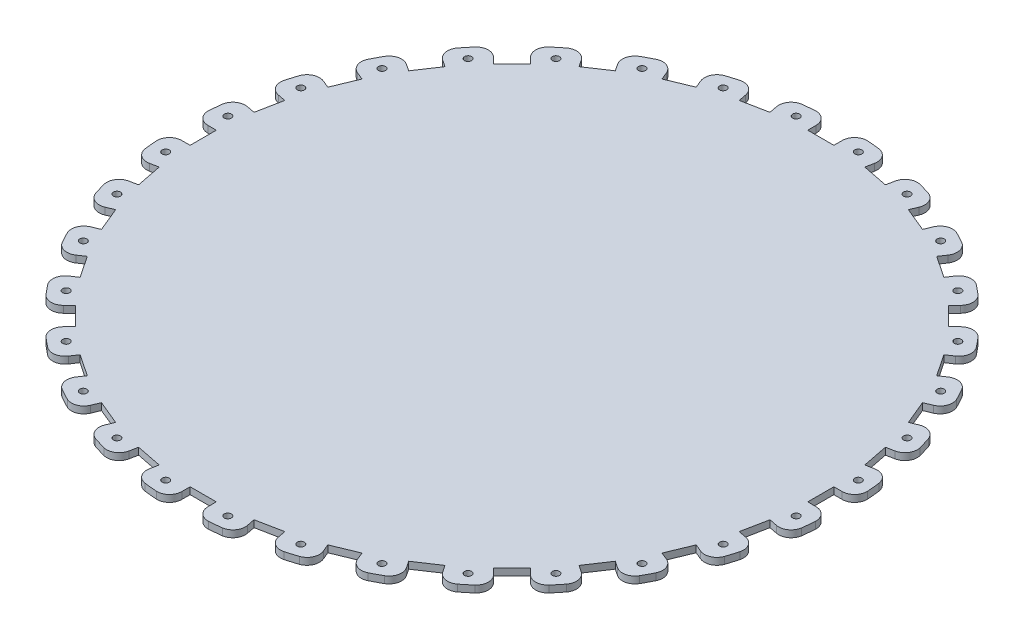
SolidWorks part; units mm, degrees
material "Maple"
ref_plane "Front" through (0, 0, 0) normal (0, 0, 1) x (1, 0, 0)
ref_plane "Top" through (0, 0, 0) normal (0, 1, 0) x (1, 0, 0)
ref_plane "Right" through (0, 0, 0) normal (1, 0, 0) x (0, 0, -1)
sketch "Sketch1" plane through (0, 0, 0) normal (0, 1, 0) x (1, 0, 0)
  line L0 (133.35, 0) -> (142.367, 0) construction
  line L1 (152.0161, 6.0325) -> (142.367, 6.0325)
  line L2 (150.272, -23.7403) -> (140.8083, -21.8578)
  line L3 (152.0161, -6.0325) -> (142.367, -6.0325)
  line L4 (142.367, 6.0325) -> (142.367, -6.0325)
  line L5 (133.35, 0) -> (142.367, -6.0325) construction
  line L6 (133.35, 0) -> (142.367, 6.0325) construction
  line L7 (147.9182, -35.5735) -> (138.4546, -33.691)
  line L8 (140.8083, -21.8578) -> (138.4546, -33.691)
  line L9 (130.7877, -26.0153) -> (139.6315, -27.7744) construction
  line L10 (130.7877, -26.0153) -> (138.4546, -33.691) construction
  line L11 (130.7877, -26.0153) -> (140.8083, -21.8578) construction
  line L12 (142.7531, -52.6007) -> (133.8385, -48.9082)
  line L13 (138.136, -63.7473) -> (129.2214, -60.0548)
  line L14 (133.8385, -48.9082) -> (129.2214, -60.0548)
  line L15 (123.1993, -51.0308) -> (131.53, -54.4815) construction
  line L16 (123.1993, -51.0308) -> (129.2214, -60.0548) construction
  line L17 (123.1993, -51.0308) -> (133.8385, -48.9082) construction
  line L18 (129.7482, -79.4398) -> (121.7253, -74.079)
  line L19 (123.0453, -89.4714) -> (115.0224, -84.1107)
  line L20 (121.7253, -74.079) -> (115.0224, -84.1107)
  line L21 (110.8765, -74.0853) -> (118.3738, -79.0949) construction
  line L22 (110.8765, -74.0853) -> (115.0224, -84.1107) construction
  line L23 (110.8765, -74.0853) -> (121.7253, -74.079) construction
  line L24 (111.7572, -103.226) -> (104.9343, -96.403)
  line L25 (103.226, -111.7572) -> (96.403, -104.9343)
  line L26 (104.9343, -96.403) -> (96.403, -104.9343)
  line L27 (94.2927, -94.2927) -> (100.6687, -100.6687) construction
  line L28 (94.2927, -94.2927) -> (96.403, -104.9343) construction
  line L29 (94.2927, -94.2927) -> (104.9343, -96.403) construction
  line L30 (89.4714, -123.0453) -> (84.1107, -115.0224)
  line L31 (79.4398, -129.7482) -> (74.079, -121.7253)
  line L32 (84.1107, -115.0224) -> (74.079, -121.7253)
  line L33 (74.0853, -110.8765) -> (79.0949, -118.3738) construction
  line L34 (74.0853, -110.8765) -> (74.079, -121.7253) construction
  line L35 (74.0853, -110.8765) -> (84.1107, -115.0224) construction
  line L36 (63.7473, -138.136) -> (60.0548, -129.2214)
  line L37 (52.6007, -142.7531) -> (48.9082, -133.8385)
  line L38 (60.0548, -129.2214) -> (48.9082, -133.8385)
  line L39 (51.0308, -123.1993) -> (54.4815, -131.53) construction
  line L40 (51.0308, -123.1993) -> (48.9082, -133.8385) construction
  line L41 (51.0308, -123.1993) -> (60.0548, -129.2214) construction
  line L42 (35.5735, -147.9182) -> (33.691, -138.4546)
  line L43 (23.7403, -150.272) -> (21.8578, -140.8083)
  line L44 (33.691, -138.4546) -> (21.8578, -140.8083)
  line L45 (26.0153, -130.7877) -> (27.7744, -139.6315) construction
  line L46 (26.0153, -130.7877) -> (21.8578, -140.8083) construction
  line L47 (26.0153, -130.7877) -> (33.691, -138.4546) construction
  line L48 (6.0325, -152.0161) -> (6.0325, -142.367)
  line L49 (-6.0325, -152.0161) -> (-6.0325, -142.367)
  line L50 (6.0325, -142.367) -> (-6.0325, -142.367)
  line L51 (0, -133.35) -> (0, -142.367) construction
  line L52 (0, -133.35) -> (-6.0325, -142.367) construction
  line L53 (0, -133.35) -> (6.0325, -142.367) construction
  line L54 (-23.7403, -150.272) -> (-21.8578, -140.8083)
  line L55 (-35.5735, -147.9182) -> (-33.691, -138.4546)
  line L56 (-21.8578, -140.8083) -> (-33.691, -138.4546)
  line L57 (-26.0153, -130.7877) -> (-27.7744, -139.6315) construction
  line L58 (-26.0153, -130.7877) -> (-33.691, -138.4546) construction
  line L59 (-26.0153, -130.7877) -> (-21.8578, -140.8083) construction
  line L60 (-52.6007, -142.7531) -> (-48.9082, -133.8385)
  line L61 (-63.7473, -138.136) -> (-60.0548, -129.2214)
  line L62 (-48.9082, -133.8385) -> (-60.0548, -129.2214)
  line L63 (-51.0308, -123.1993) -> (-54.4815, -131.53) construction
  line L64 (-51.0308, -123.1993) -> (-60.0548, -129.2214) construction
  line L65 (-51.0308, -123.1993) -> (-48.9082, -133.8385) construction
  line L66 (-79.4398, -129.7482) -> (-74.079, -121.7253)
  line L67 (-89.4714, -123.0453) -> (-84.1107, -115.0224)
  line L68 (-74.079, -121.7253) -> (-84.1107, -115.0224)
  line L69 (-74.0853, -110.8765) -> (-79.0949, -118.3738) construction
  line L70 (-74.0853, -110.8765) -> (-84.1107, -115.0224) construction
  line L71 (-74.0853, -110.8765) -> (-74.079, -121.7253) construction
  line L72 (-103.226, -111.7572) -> (-96.403, -104.9343)
  line L73 (-111.7572, -103.226) -> (-104.9343, -96.403)
  line L74 (-96.403, -104.9343) -> (-104.9343, -96.403)
  line L75 (-94.2927, -94.2927) -> (-100.6687, -100.6687) construction
  line L76 (-94.2927, -94.2927) -> (-104.9343, -96.403) construction
  line L77 (-94.2927, -94.2927) -> (-96.403, -104.9343) construction
  line L78 (-123.0453, -89.4714) -> (-115.0224, -84.1107)
  line L79 (-129.7482, -79.4398) -> (-121.7253, -74.079)
  line L80 (-115.0224, -84.1107) -> (-121.7253, -74.079)
  line L81 (-110.8765, -74.0853) -> (-118.3738, -79.0949) construction
  line L82 (-110.8765, -74.0853) -> (-121.7253, -74.079) construction
  line L83 (-110.8765, -74.0853) -> (-115.0224, -84.1107) construction
  line L84 (-138.136, -63.7473) -> (-129.2214, -60.0548)
  line L85 (-142.7531, -52.6007) -> (-133.8385, -48.9082)
  line L86 (-129.2214, -60.0548) -> (-133.8385, -48.9082)
  line L87 (-123.1993, -51.0308) -> (-131.53, -54.4815) construction
  line L88 (-123.1993, -51.0308) -> (-133.8385, -48.9082) construction
  line L89 (-123.1993, -51.0308) -> (-129.2214, -60.0548) construction
  line L90 (-147.9182, -35.5735) -> (-138.4546, -33.691)
  line L91 (-150.272, -23.7403) -> (-140.8083, -21.8578)
  line L92 (-138.4546, -33.691) -> (-140.8083, -21.8578)
  line L93 (-130.7877, -26.0153) -> (-139.6315, -27.7744) construction
  line L94 (-130.7877, -26.0153) -> (-140.8083, -21.8578) construction
  line L95 (-130.7877, -26.0153) -> (-138.4546, -33.691) construction
  line L96 (-152.0161, -6.0325) -> (-142.367, -6.0325)
  line L97 (-152.0161, 6.0325) -> (-142.367, 6.0325)
  line L98 (-142.367, -6.0325) -> (-142.367, 6.0325)
  line L99 (-133.35, 0) -> (-142.367, 0) construction
  line L100 (-133.35, 0) -> (-142.367, 6.0325) construction
  line L101 (-133.35, 0) -> (-142.367, -6.0325) construction
  line L102 (-150.272, 23.7403) -> (-140.8083, 21.8578)
  line L103 (-147.9182, 35.5735) -> (-138.4546, 33.691)
  line L104 (-140.8083, 21.8578) -> (-138.4546, 33.691)
  line L105 (-130.7877, 26.0153) -> (-139.6315, 27.7744) construction
  line L106 (-130.7877, 26.0153) -> (-138.4546, 33.691) construction
  line L107 (-130.7877, 26.0153) -> (-140.8083, 21.8578) construction
  line L108 (-142.7531, 52.6007) -> (-133.8385, 48.9082)
  line L109 (-138.136, 63.7473) -> (-129.2214, 60.0548)
  line L110 (-133.8385, 48.9082) -> (-129.2214, 60.0548)
  line L111 (-123.1993, 51.0308) -> (-131.53, 54.4815) construction
  line L112 (-123.1993, 51.0308) -> (-129.2214, 60.0548) construction
  line L113 (-123.1993, 51.0308) -> (-133.8385, 48.9082) construction
  line L114 (-129.7482, 79.4398) -> (-121.7253, 74.079)
  line L115 (-123.0453, 89.4714) -> (-115.0224, 84.1107)
  line L116 (-121.7253, 74.079) -> (-115.0224, 84.1107)
  line L117 (-110.8765, 74.0853) -> (-118.3738, 79.0949) construction
  line L118 (-110.8765, 74.0853) -> (-115.0224, 84.1107) construction
  line L119 (-110.8765, 74.0853) -> (-121.7253, 74.079) construction
  line L120 (-111.7572, 103.226) -> (-104.9343, 96.403)
  line L121 (-103.226, 111.7572) -> (-96.403, 104.9343)
  line L122 (-104.9343, 96.403) -> (-96.403, 104.9343)
  line L123 (-94.2927, 94.2927) -> (-100.6687, 100.6687) construction
  line L124 (-94.2927, 94.2927) -> (-96.403, 104.9343) construction
  line L125 (-94.2927, 94.2927) -> (-104.9343, 96.403) construction
  line L126 (-89.4714, 123.0453) -> (-84.1107, 115.0224)
  line L127 (-79.4398, 129.7482) -> (-74.079, 121.7253)
  line L128 (-84.1107, 115.0224) -> (-74.079, 121.7253)
  line L129 (-74.0853, 110.8765) -> (-79.0949, 118.3738) construction
  line L130 (-74.0853, 110.8765) -> (-74.079, 121.7253) construction
  line L131 (-74.0853, 110.8765) -> (-84.1107, 115.0224) construction
  line L132 (-63.7473, 138.136) -> (-60.0548, 129.2214)
  line L133 (-52.6007, 142.7531) -> (-48.9082, 133.8385)
  line L134 (-60.0548, 129.2214) -> (-48.9082, 133.8385)
  line L135 (-51.0308, 123.1993) -> (-54.4815, 131.53) construction
  line L136 (-51.0308, 123.1993) -> (-48.9082, 133.8385) construction
  line L137 (-51.0308, 123.1993) -> (-60.0548, 129.2214) construction
  line L138 (-35.5735, 147.9182) -> (-33.691, 138.4546)
  line L139 (-23.7403, 150.272) -> (-21.8578, 140.8083)
  line L140 (-33.691, 138.4546) -> (-21.8578, 140.8083)
  line L141 (-26.0153, 130.7877) -> (-27.7744, 139.6315) construction
  line L142 (-26.0153, 130.7877) -> (-21.8578, 140.8083) construction
  line L143 (-26.0153, 130.7877) -> (-33.691, 138.4546) construction
  line L144 (-6.0325, 152.0161) -> (-6.0325, 142.367)
  line L145 (6.0325, 152.0161) -> (6.0325, 142.367)
  line L146 (-6.0325, 142.367) -> (6.0325, 142.367)
  line L147 (0, 133.35) -> (0, 142.367) construction
  line L148 (0, 133.35) -> (6.0325, 142.367) construction
  line L149 (0, 133.35) -> (-6.0325, 142.367) construction
  line L150 (23.7403, 150.272) -> (21.8578, 140.8083)
  line L151 (35.5735, 147.9182) -> (33.691, 138.4546)
  line L152 (21.8578, 140.8083) -> (33.691, 138.4546)
  line L153 (26.0153, 130.7877) -> (27.7744, 139.6315) construction
  line L154 (26.0153, 130.7877) -> (33.691, 138.4546) construction
  line L155 (26.0153, 130.7877) -> (21.8578, 140.8083) construction
  line L156 (52.6007, 142.7531) -> (48.9082, 133.8385)
  line L157 (63.7473, 138.136) -> (60.0548, 129.2214)
  line L158 (48.9082, 133.8385) -> (60.0548, 129.2214)
  line L159 (51.0308, 123.1993) -> (54.4815, 131.53) construction
  line L160 (51.0308, 123.1993) -> (60.0548, 129.2214) construction
  line L161 (51.0308, 123.1993) -> (48.9082, 133.8385) construction
  line L162 (79.4398, 129.7482) -> (74.079, 121.7253)
  line L163 (89.4714, 123.0453) -> (84.1107, 115.0224)
  line L164 (74.079, 121.7253) -> (84.1107, 115.0224)
  line L165 (74.0853, 110.8765) -> (79.0949, 118.3738) construction
  line L166 (74.0853, 110.8765) -> (84.1107, 115.0224) construction
  line L167 (74.0853, 110.8765) -> (74.079, 121.7253) construction
  line L168 (103.226, 111.7572) -> (96.403, 104.9343)
  line L169 (111.7572, 103.226) -> (104.9343, 96.403)
  line L170 (96.403, 104.9343) -> (104.9343, 96.403)
  line L171 (94.2927, 94.2927) -> (100.6687, 100.6687) construction
  line L172 (94.2927, 94.2927) -> (104.9343, 96.403) construction
  line L173 (94.2927, 94.2927) -> (96.403, 104.9343) construction
  line L174 (123.0453, 89.4714) -> (115.0224, 84.1107)
  line L175 (129.7482, 79.4398) -> (121.7253, 74.079)
  line L176 (115.0224, 84.1107) -> (121.7253, 74.079)
  line L177 (110.8765, 74.0853) -> (118.3738, 79.0949) construction
  line L178 (110.8765, 74.0853) -> (121.7253, 74.079) construction
  line L179 (110.8765, 74.0853) -> (115.0224, 84.1107) construction
  line L180 (138.136, 63.7473) -> (129.2214, 60.0548)
  line L181 (142.7531, 52.6007) -> (133.8385, 48.9082)
  line L182 (129.2214, 60.0548) -> (133.8385, 48.9082)
  line L183 (123.1993, 51.0308) -> (131.53, 54.4815) construction
  line L184 (123.1993, 51.0308) -> (133.8385, 48.9082) construction
  line L185 (123.1993, 51.0308) -> (129.2214, 60.0548) construction
  line L186 (147.9182, 35.5735) -> (138.4546, 33.691)
  line L187 (150.272, 23.7403) -> (140.8083, 21.8578)
  line L188 (138.4546, 33.691) -> (140.8083, 21.8578)
  line L189 (130.7877, 26.0153) -> (139.6315, 27.7744) construction
  line L190 (130.7877, 26.0153) -> (140.8083, 21.8578) construction
  line L191 (130.7877, 26.0153) -> (138.4546, 33.691) construction
  arc A0 (152.2699, 6.297) -> (152.2699, -6.297) centre (0, 0) ccw
  circle A1 centre (0, 0) radius 133.35
  arc A2 (152.0161, 6.0325) -> (152.2699, 6.297) centre (152.0161, 6.2865) ccw
  arc A3 (152.0161, -6.0325) -> (152.2699, -6.297) centre (152.0161, -6.2865) cw
  arc A4 (150.272, -23.7403) -> (150.5725, -23.5304) centre (150.3216, -23.4912) ccw
  arc A5 (147.9182, -35.5735) -> (148.1155, -35.8824) centre (147.8687, -35.8226) cw
  arc A6 (142.7531, -52.6007) -> (143.0888, -52.4535) centre (142.8503, -52.3661) ccw
  arc A7 (138.136, -63.7473) -> (138.2692, -64.0888) centre (138.0388, -63.982) cw
  arc A8 (129.7482, -79.4398) -> (130.1062, -79.3608) centre (129.8893, -79.2286) ccw
  arc A9 (123.0453, -89.4714) -> (123.1093, -89.8324) centre (122.9041, -89.6826) cw
  arc A10 (111.7572, -103.226) -> (112.1237, -103.2184) centre (111.9368, -103.0464) ccw
  arc A11 (103.226, -111.7572) -> (103.2184, -112.1237) centre (103.0464, -111.9368) cw
  arc A12 (89.4714, -123.0453) -> (89.8324, -123.1093) centre (89.6826, -122.9041) ccw
  arc A13 (79.4398, -129.7482) -> (79.3608, -130.1062) centre (79.2286, -129.8893) cw
  arc A14 (63.7473, -138.136) -> (64.0888, -138.2692) centre (63.982, -138.0388) ccw
  arc A15 (52.6007, -142.7531) -> (52.4535, -143.0888) centre (52.3661, -142.8503) cw
  arc A16 (35.5735, -147.9182) -> (35.8824, -148.1155) centre (35.8226, -147.8687) ccw
  arc A17 (23.7403, -150.272) -> (23.5304, -150.5725) centre (23.4912, -150.3216) cw
  arc A18 (6.0325, -152.0161) -> (6.297, -152.2699) centre (6.2865, -152.0161) ccw
  arc A19 (-6.0325, -152.0161) -> (-6.297, -152.2699) centre (-6.2865, -152.0161) cw
  arc A20 (-23.7403, -150.272) -> (-23.5304, -150.5725) centre (-23.4912, -150.3216) ccw
  arc A21 (-35.5735, -147.9182) -> (-35.8824, -148.1155) centre (-35.8226, -147.8687) cw
  arc A22 (-52.6007, -142.7531) -> (-52.4535, -143.0888) centre (-52.3661, -142.8503) ccw
  arc A23 (-63.7473, -138.136) -> (-64.0888, -138.2692) centre (-63.982, -138.0388) cw
  arc A24 (-79.4398, -129.7482) -> (-79.3608, -130.1062) centre (-79.2286, -129.8893) ccw
  arc A25 (-89.4714, -123.0453) -> (-89.8324, -123.1093) centre (-89.6826, -122.9041) cw
  arc A26 (-103.226, -111.7572) -> (-103.2184, -112.1237) centre (-103.0464, -111.9368) ccw
  arc A27 (-111.7572, -103.226) -> (-112.1237, -103.2184) centre (-111.9368, -103.0464) cw
  arc A28 (-123.0453, -89.4714) -> (-123.1093, -89.8324) centre (-122.9041, -89.6826) ccw
  arc A29 (-129.7482, -79.4398) -> (-130.1062, -79.3608) centre (-129.8893, -79.2286) cw
  arc A30 (-138.136, -63.7473) -> (-138.2692, -64.0888) centre (-138.0388, -63.982) ccw
  arc A31 (-142.7531, -52.6007) -> (-143.0888, -52.4535) centre (-142.8503, -52.3661) cw
  arc A32 (-147.9182, -35.5735) -> (-148.1155, -35.8824) centre (-147.8687, -35.8226) ccw
  arc A33 (-150.272, -23.7403) -> (-150.5725, -23.5304) centre (-150.3216, -23.4912) cw
  arc A34 (-152.0161, -6.0325) -> (-152.2699, -6.297) centre (-152.0161, -6.2865) ccw
  arc A35 (-152.0161, 6.0325) -> (-152.2699, 6.297) centre (-152.0161, 6.2865) cw
  arc A36 (-150.272, 23.7403) -> (-150.5725, 23.5304) centre (-150.3216, 23.4912) ccw
  arc A37 (-147.9182, 35.5735) -> (-148.1155, 35.8824) centre (-147.8687, 35.8226) cw
  arc A38 (-142.7531, 52.6007) -> (-143.0888, 52.4535) centre (-142.8503, 52.3661) ccw
  arc A39 (-138.136, 63.7473) -> (-138.2692, 64.0888) centre (-138.0388, 63.982) cw
  arc A40 (-129.7482, 79.4398) -> (-130.1062, 79.3608) centre (-129.8893, 79.2286) ccw
  arc A41 (-123.0453, 89.4714) -> (-123.1093, 89.8324) centre (-122.9041, 89.6826) cw
  arc A42 (-111.7572, 103.226) -> (-112.1237, 103.2184) centre (-111.9368, 103.0464) ccw
  arc A43 (-103.226, 111.7572) -> (-103.2184, 112.1237) centre (-103.0464, 111.9368) cw
  arc A44 (-89.4714, 123.0453) -> (-89.8324, 123.1093) centre (-89.6826, 122.9041) ccw
  arc A45 (-79.4398, 129.7482) -> (-79.3608, 130.1062) centre (-79.2286, 129.8893) cw
  arc A46 (-63.7473, 138.136) -> (-64.0888, 138.2692) centre (-63.982, 138.0388) ccw
  arc A47 (-52.6007, 142.7531) -> (-52.4535, 143.0888) centre (-52.3661, 142.8503) cw
  arc A48 (-35.5735, 147.9182) -> (-35.8824, 148.1155) centre (-35.8226, 147.8687) ccw
  arc A49 (-23.7403, 150.272) -> (-23.5304, 150.5725) centre (-23.4912, 150.3216) cw
  arc A50 (-6.0325, 152.0161) -> (-6.297, 152.2699) centre (-6.2865, 152.0161) ccw
  arc A51 (6.0325, 152.0161) -> (6.297, 152.2699) centre (6.2865, 152.0161) cw
  arc A52 (23.7403, 150.272) -> (23.5304, 150.5725) centre (23.4912, 150.3216) ccw
  arc A53 (35.5735, 147.9182) -> (35.8824, 148.1155) centre (35.8226, 147.8687) cw
  arc A54 (52.6007, 142.7531) -> (52.4535, 143.0888) centre (52.3661, 142.8503) ccw
  arc A55 (63.7473, 138.136) -> (64.0888, 138.2692) centre (63.982, 138.0388) cw
  arc A56 (79.4398, 129.7482) -> (79.3608, 130.1062) centre (79.2286, 129.8893) ccw
  arc A57 (89.4714, 123.0453) -> (89.8324, 123.1093) centre (89.6826, 122.9041) cw
  arc A58 (103.226, 111.7572) -> (103.2184, 112.1237) centre (103.0464, 111.9368) ccw
  arc A59 (111.7572, 103.226) -> (112.1237, 103.2184) centre (111.9368, 103.0464) cw
  arc A60 (123.0453, 89.4714) -> (123.1093, 89.8324) centre (122.9041, 89.6826) ccw
  arc A61 (129.7482, 79.4398) -> (130.1062, 79.3608) centre (129.8893, 79.2286) cw
  arc A62 (138.136, 63.7473) -> (138.2692, 64.0888) centre (138.0388, 63.982) ccw
  arc A63 (142.7531, 52.6007) -> (143.0888, 52.4535) centre (142.8503, 52.3661) cw
  arc A64 (147.9182, 35.5735) -> (148.1155, 35.8824) centre (147.8687, 35.8226) ccw
  arc A65 (150.272, 23.7403) -> (150.5725, 23.5304) centre (150.3216, 23.4912) cw
  point P4 (133.35, 0)
  point P231 (0, 0)
  point P328 (0, 0)
  dimension "D1" = 304.8
  dimension "D2" = 19.05
  dimension "D3" = 12.065
  dimension "D5" = 0.254
  dimension "D4" = 9.017
extrude "Boss-Extrude1" add sketch "Sketch1" along normal blind 3.175 contours A0 A1 | A1 region at (147.1915, 0, -10.3393) region at (0, 0, 0)
sketch "Sketch5" plane through (0, 0, 0) normal (0, -1, 0) x (1, 0, 0)
  line L0 (0, 0) -> (151.6662, 14.9378) construction
  line L1 (-117.8068, 96.6815) -> (0, 0) construction
  line L2 (-123.0453, 89.4714) -> (-115.0224, 84.1107) construction
  line L3 (-115.0224, 84.1107) -> (-121.7253, 74.079) construction
  line L4 (-111.9442, 103.413) -> (-107.6284, 99.0971)
  line L5 (-123.2652, 89.6184) -> (-118.1903, 86.2274)
  arc A0 (152.2699, 6.297) -> (150.5725, 23.5304) centre (0, 0) ccw construction
  circle A1 centre (145.3467, 14.3154) radius 1.6383
  circle A2 centre (0, 0) radius 146.05 construction
  arc A3 (-112.1237, 103.2184) -> (-123.1093, 89.8324) centre (0, 0) ccw construction
  circle A4 centre (-112.8982, 92.6531) radius 1.6383
  arc A5 (-118.1903, 86.2274) -> (-119.4018, 94.7047) centre (-114.9951, 91.0093) cw
  arc A6 (-119.4018, 94.7047) -> (-123.2652, 89.6184) centre (0, 0) ccw
  arc A7 (-116.1791, 98.6316) -> (-111.9442, 103.413) centre (0, 0) cw
  arc A8 (-107.6284, 99.0971) -> (-116.1791, 98.6316) centre (-111.695, 95.0305) ccw
  dimension "D1" = 292.1
  dimension "D2" = 3.2766
  dimension "D3" = 3.2766
  dimension "D4" = 3.81
  dimension "D5" = 2.54
extrude "Cut-Extrude1" cut sketch "Sketch5" against normal through all contours A4 region at (-112.8982, 0, 92.6531)
ref_axis "Axis1" through (0, 50, 0) along (0, -1, 0)
extrude "Cut-Extrude2" cut sketch "Sketch5<3>" against normal through all contours A5 A6 L5 | A8 L4 A7 region at (-111.9152, 0, 101.4078) region at (-121.2929, 0, 89.9811)
sketch "Sketch5<3>" plane through (0, 0, 0) normal (0, -1, 0) x (1, 0, 0) same geometry as "Sketch5"
pattern_circular "CirPattern2" count 32 over 360 about axis through (0, 50, 0) along (0, -1, 0) of "Cut-Extrude2", "Cut-Extrude1"
